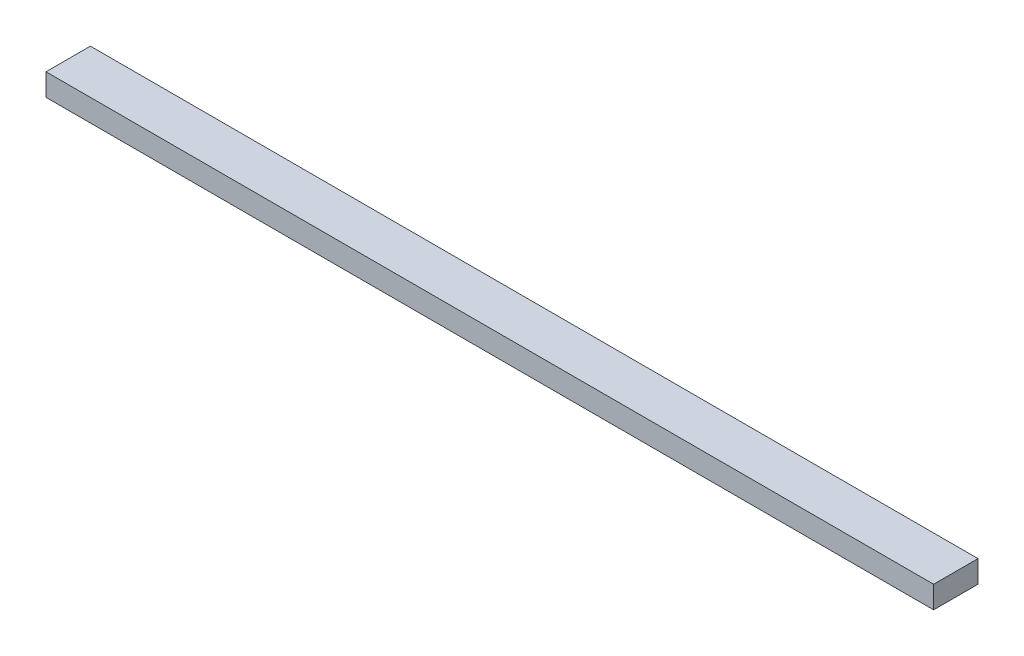
SolidWorks part; units mm, degrees
ref_plane "Front Plane" through (0, 0, 0) normal (0, 0, 1) x (1, 0, 0)
ref_plane "Top Plane" through (0, 0, 0) normal (0, 1, 0) x (1, 0, 0)
ref_plane "Right Plane" through (0, 0, 0) normal (1, 0, 0) x (0, 0, -1)
sketch "Sketch1" plane through (0, 0, 0) normal (0, 0, 1) x (1, 0, 0)
  line L1 (-127, 3.175) -> (127, 3.175)
  line L2 (-127, 3.175) -> (-127, -3.175)
  line L3 (-127, -3.175) -> (127, -3.175)
  line L4 (127, 3.175) -> (127, -3.175)
  line L5 (-127, 3.175) -> (127, -3.175) construction
  line L6 (-127, -3.175) -> (127, 3.175) construction
  point P0 (0, 0)
  dimension "D1" = 254
  dimension "D2" = 6.35
extrude "Boss-Extrude1" add sketch "Sketch1" along normal blind 12.7
